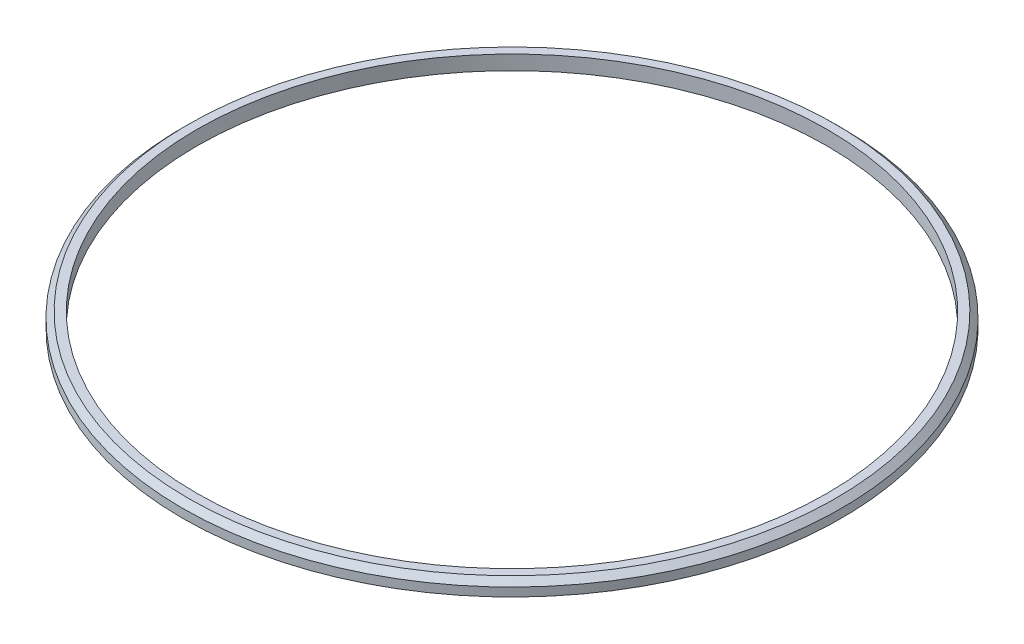
SolidWorks part; units mm, degrees
material "PETG"
ref_plane "Front Plane" through (0, 0, 0) normal (0, 0, 1) x (1, 0, 0)
ref_plane "Top Plane" through (0, 0, 0) normal (0, 1, 0) x (1, 0, 0)
ref_plane "Right Plane" through (0, 0, 0) normal (1, 0, 0) x (0, 0, -1)
sketch "Sketch1" plane through (0, 0, 0) normal (0, 1, 0) x (1, 0, 0)
  circle A0 centre (0, 0) radius 57.25
  circle A1 centre (0, 0) radius 54.75
  dimension "D1" = 114.5
  dimension "D2" = 2.5
extrude "Boss-Extrude1" add sketch "Sketch1" along normal blind 2.5
chamfer "Chamfer1" distance 1 angle 45 1 edges at (0, 2.5, 57.25)
